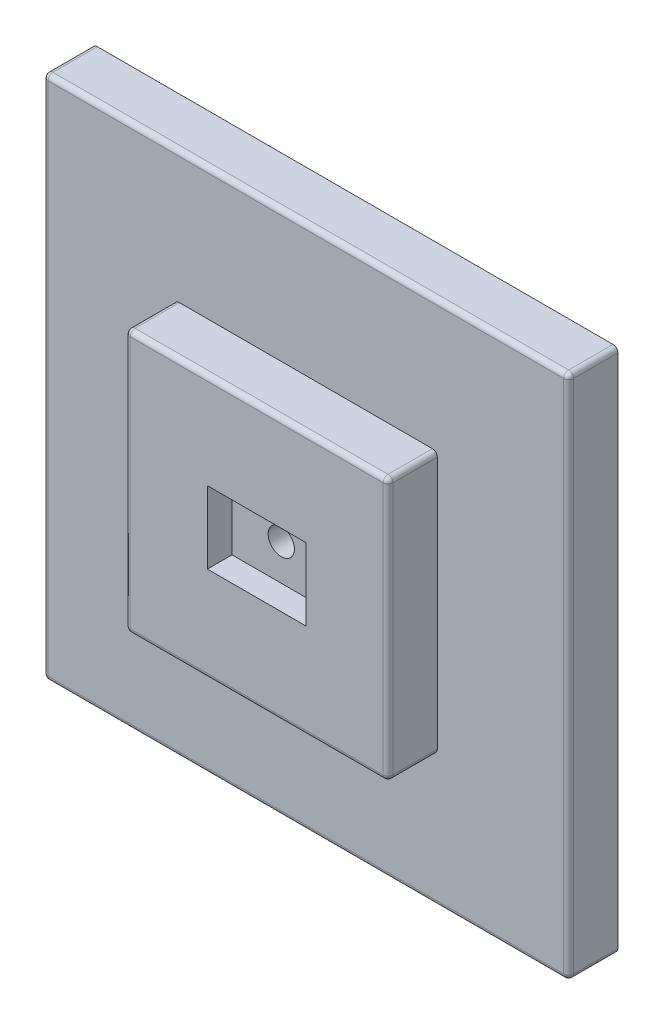
SolidWorks part; units mm, degrees
ref_plane "Front Plane" through (0, 0, 0) normal (0, 0, 1) x (1, 0, 0)
ref_plane "Top Plane" through (0, 0, 0) normal (0, 1, 0) x (1, 0, 0)
ref_plane "Right Plane" through (0, 0, 0) normal (1, 0, 0) x (0, 0, -1)
sketch "Sketch1" plane through (0, 0, 0) normal (0, 0, 1) x (1, 0, 0)
  line L0 (0, 80) -> (160, 80) construction
  line L1 (0, 0) -> (160, 0)
  line L2 (0, 0) -> (0, 160)
  line L3 (0, 160) -> (160, 160)
  line L4 (160, 0) -> (160, 160)
  line L5 (80, 0) -> (80, 160) construction
  line L6 (80, 80) -> (80, 91)
  line L7 (40, 120) -> (120, 120)
  line L8 (40, 120) -> (40, 40)
  line L9 (40, 40) -> (120, 40)
  line L10 (120, 120) -> (120, 40)
  line L11 (80, 80) -> (80, 69)
  line L12 (80, 69) -> (95, 69)
  line L13 (80, 69) -> (65, 69)
  line L14 (95, 69) -> (95, 91)
  line L15 (95, 91) -> (65, 91)
  line L16 (65, 91) -> (65, 69)
  dimension "D1" = 160
  dimension "D2" = 160
  dimension "D3" = 40
  dimension "D4" = 40
  dimension "D5" = 40
  dimension "D6" = 40
  dimension "D7" = 80
  dimension "D8" = 11
  dimension "D9" = 11
  dimension "D10" = 15
  dimension "D11" = 15
extrude "Boss-Extrude1" add sketch "Sketch1" along normal blind 15 contours L1 L4 L3 L2 L7 L10 L9 L8 region at (2.2627, 80, 0)
extrude "Boss-Extrude2" add sketch "Sketch1<5>" along normal blind 30 contours L10 L7 L8 L9 L16 L15 L14 L12 L13 region at (80, 118.8686, 0)
sketch "Sketch1<5>" plane through (0, 0, 0) normal (0, 0, 1) x (1, 0, 0) same geometry as "Sketch1"
extrude "Boss-Extrude3" add sketch "Sketch1<6>" along normal blind 22.5 contours L14 L15 L6 L11 L12 | L15 L16 L13 L11 L6 region at (72.5, 80, 0) region at (87.5, 80, 0)
sketch "Sketch1<6>" plane through (0, 0, 0) normal (0, 0, 1) x (1, 0, 0) same geometry as "Sketch1"
sketch "Sketch2" plane through (0, 0, 22.5) normal (0, 0, 1) x (1, 0, 0)
  line L0 (95, 69) -> (65, 91) construction
  circle A0 centre (80, 80) radius 4
  dimension "D1" = 8
extrude "Cut-Extrude2" cut sketch "Sketch2" against normal blind 22.5
sketch "Sketch3" plane through (0, 0, 0) normal (0, 0, -1) x (-1, 0, 0)
  circle A0 centre (-80, 80) radius 7.5
  dimension "D1" = 15
extrude "Cut-Extrude3" cut sketch "Sketch3" against normal blind 5 contours A0
fillet "Fillet1" radius 1.5 16 edges at (0, 0, 7.5) (80, 0, 15) (160, 0, 7.5) (160, 160, 7.5) (160, 80, 15) (0, 160, 7.5) (80, 160, 15) (0, 80, 15) (40, 40, 22.5) (40, 120, 22.5) (120, 120, 22.5) (120, 40, 22.5) (40, 80, 30) (120, 80, 30) (80, 120, 30) (80, 40, 30)
